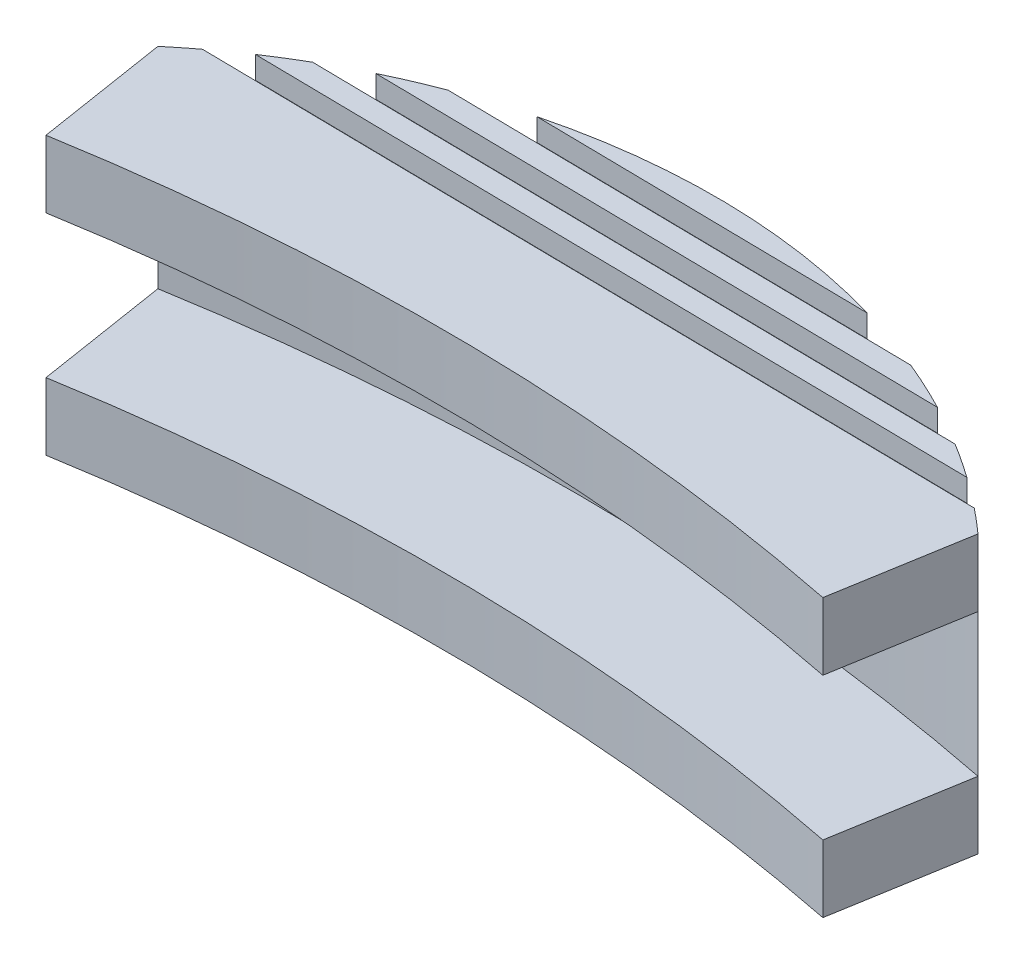
SolidWorks part; units mm, degrees
ref_plane "Front Plane" through (0, 0, 0) normal (0, 0, 1) x (1, 0, 0)
ref_plane "Top Plane" through (0, 0, 0) normal (0, 1, 0) x (1, 0, 0)
ref_plane "Right Plane" through (0, 0, 0) normal (1, 0, 0) x (0, 0, -1)
sketch "Sketch1" plane through (0, -32.3616, 0) normal (0, -1, 0) x (1, 0, 0)
  line L0 (-28.869, -307.0148) -> (-29.869, -301.0961)
  line L1 (-65.9817, -307.5573) -> (-65.0445, -301.6306)
  arc A0 (-28.869, -307.0148) -> (-65.9817, -307.5573) centre (-48.9061, -205.9825) cw
  arc A1 (-48.9061, -308.9825) -> (-48.9061, -102.9825) centre (-48.9061, -205.9825) ccw construction
  arc A2 (-48.9061, -102.9825) -> (-48.9061, -308.9825) centre (-48.9061, -205.9825) ccw construction
  arc A3 (-48.9061, -302.9825) -> (-25.267, -300.058) centre (-48.9061, -205.9825) ccw construction
  arc A4 (-72.5452, -300.058) -> (-48.9061, -302.9825) centre (-48.9061, -205.9825) ccw construction
  arc A5 (-29.869, -301.0961) -> (-65.0445, -301.6306) centre (-48.9061, -205.9825) cw
  dimension "D2" = 1
  dimension "D1" = 1
extrude "Boss-Extrude1" add sketch "Sketch1" along normal blind 3
extrude "Boss-Extrude2" add sketch "Sketch1<2>" against normal blind 3 from offset 6.36 separate body offset against normal yes
sketch "Sketch1<2>" plane through (0, -32.3616, 0) normal (0, -1, 0) x (1, 0, 0) same geometry as "Sketch1"
sketch "Sketch2" plane through (0, -26.0016, 0) normal (0, -1, 0) x (-1, 0, 0)
  arc A2 (65.9817, 307.5573) -> (28.869, 307.0148) centre (48.9061, 205.9825) ccw
  arc A3 (65.9817, 307.5573) -> (28.869, 307.0148) centre (47.7397, 285.7766) ccw
  arc M7 (65.9817, 307.5573) -> (28.869, 307.0148) centre (48.9061, 205.9825) ccw
extrude "Boss-Extrude3" add sketch "Sketch2" against normal up to surface (3 mm away) and the other way up to surface (9.36 mm away) contours A3 M7 | A3 A2 region at (-47.3749, -26.0016, -310.738) up to face at (-47.4288, -23.0016, -305.1481) other way up to face at (-47.4288, -35.3616, -305.1481)
sketch "Sketch4" plane through (0, -23.0016, 0) normal (0, 1, 0) x (1, 0, 0)
  line L0 (-64.8725, 308.4401) -> (-29.9519, 307.9297)
  line L1 (-47.4122, 308.1849) -> (-47.1551, 325.7741) construction
  line L2 (-47.1551, 325.7741) -> (-52.6184, 325.8539) construction
  line L3 (-63.4927, 309.42) -> (-31.3025, 308.9495)
  line L4 (-61.9171, 310.3971) -> (-32.8489, 309.9722)
  line L5 (-60.0738, 311.3703) -> (-34.6629, 310.9988)
  line L6 (-57.8237, 312.3375) -> (-36.8838, 312.0314)
  line L7 (-54.8097, 313.2935) -> (-39.8685, 313.0751)
  line L10 (-65.9686, 308.4561) -> (-28.8558, 307.9136) construction
  line L11 (-65.954, 309.456) -> (-28.8412, 308.9135) construction
  line L12 (-65.9393, 310.4559) -> (-28.8266, 309.9134) construction
  line L13 (-65.9247, 311.4558) -> (-28.812, 310.9133) construction
  line L14 (-65.9101, 312.4557) -> (-28.7974, 311.9132) construction
  line L15 (-65.8955, 313.4556) -> (-28.7827, 312.9131) construction
  arc A0 (-28.869, 307.0148) -> (-65.9817, 307.5573) centre (-47.7397, 285.7766) ccw construction
  arc A1 (-64.8725, 308.4401) -> (-29.9519, 307.9297) centre (-47.7397, 285.7766) cw
  point P17 (-47.3245, 314.1842)
  point P18 (-65.8809, 314.4555)
  point P22 (-28.7681, 313.913)
  arc M7 (-28.869, 307.0148) -> (-65.9817, 307.5573) centre (-47.7397, 285.7766) ccw
  dimension "D6" = 6
  dimension "D1" = 1
  dimension "D2" = 1
  dimension "D3" = 1
  dimension "D4" = 1
  dimension "D5" = 1
extrude "Cut-Extrude1" cut sketch "Sketch4" against normal blind 1 contours L3 L0 M7 | L5 L4 M7 | L7 L6 M7 region at (-47.405, -23.0016, -308.6781) region at (-47.3758, -23.0016, -310.6735) region at (-47.3468, -23.0016, -312.657)
ref_plane "Plane1" through (0, -29.1816, 0) normal (0, -1, 0) x (-1, 0, 0)
mirror "Mirror1" about plane through (0, -29.1816, 0) normal (0, -1, 0) of "Cut-Extrude1"
